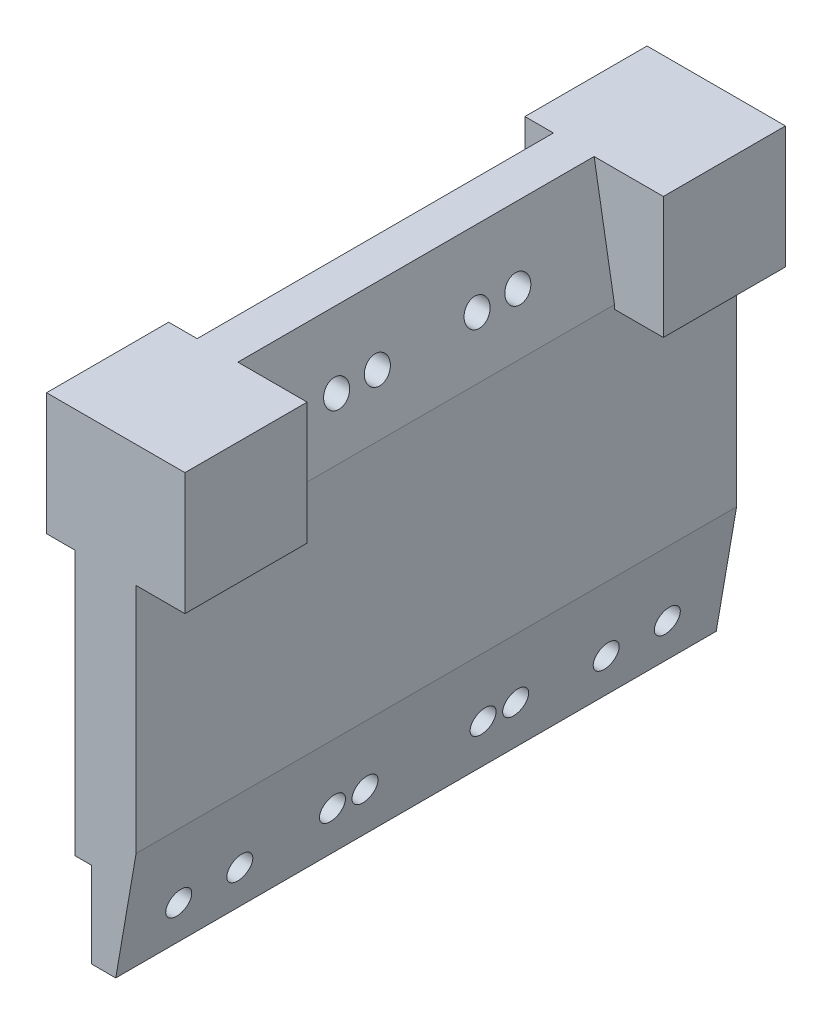
SolidWorks part; units mm, degrees
ref_plane "Front Plane" through (0, 0, 0) normal (0, 0, 1) x (1, 0, 0)
ref_plane "Top Plane" through (0, 0, 0) normal (0, 1, 0) x (1, 0, 0)
ref_plane "Right Plane" through (0, 0, 0) normal (1, 0, 0) x (0, 0, -1)
sketch "Sketch1" plane through (0, 0, 0) normal (0, 0, 1) x (1, 0, 0)
  line L1 (0, 0) -> (5, 0)
  line L2 (0, 0) -> (0, -116)
  line L3 (0, -116) -> (5, -116)
  line L4 (5, 0) -> (5, -116)
  line L5 (5, 0) -> (15, 0)
  line L6 (5, 0) -> (5, -116)
  line L7 (5, -116) -> (15, -116)
  line L8 (15, 0) -> (15, -116)
  line L9 (15, -58) -> (15, 0)
  line L10 (10, 0) -> (15, -29)
  line L11 (15, -29) -> (15, -58)
  line L13 (15, -58) -> (15, -116)
  line L14 (15, -87) -> (10, -116)
  dimension "D1" = 5
  dimension "D2" = 116
  dimension "D3" = 10
extrude "Boss-Extrude1" add sketch "Sketch1" along normal blind 73.75 and the other way blind 73.75 contours L14 L8 L9 L10 L5 L4 L7 | L4 L1 L2 L3 region at (2.5, -58, 0) region at (9.5238, -58, 0)
sketch "Sketch2" plane through (15, 0, 0) normal (1, 0, 0) x (0, 0, -1)
  line L0 (73.75, -87) -> (73.75, -116) construction
  line L1 (73.75, -116) -> (-73.75, -116) construction
  line L3 (73.75, -93.3455) -> (-73.75, -93.3455) construction
  line L4 (-73.75, -87) -> (-73.75, -116) construction
  line L5 (-73.75, -93.3455) -> (0, -93.3455) construction
  line L6 (0, -93.3455) -> (0, -116) construction
  circle A0 centre (60, -106) radius 1.5
  circle A1 centre (45, -106) radius 1.5
  circle A2 centre (22.5, -104.5) radius 1.5
  circle A3 centre (14.5, -104.5) radius 1.5
  circle A4 centre (-14.5, -104.5) radius 1.5
  circle A5 centre (-22.5, -104.5) radius 1.5
  circle A6 centre (-45, -106) radius 1.5
  circle A7 centre (-60, -106) radius 1.5
  dimension "D1" = 3
  dimension "D2" = 13.75
  dimension "D3" = 10
  dimension "D5" = 15
  dimension "D6" = 3
  dimension "D7" = 11.5
  dimension "D8" = 51.25
  dimension "D10" = 8
  dimension "D4" = 2
  dimension "D9" = 2
extrude "Cut-Extrude1" cut sketch "Sketch2" against normal through all
sketch "Sketch3" plane through (15, 0, 0) normal (1, 0, 0) x (0, 0, -1)
  line L0 (0, 0) -> (0, -111.271) construction
  line L35 (73.75, 0) -> (-73.75, 0) construction
  circle A0 centre (60, -106) radius 3.15
  circle A1 centre (45, -106) radius 3.15
  circle A2 centre (22.5, -104.5) radius 3.15
  circle A3 centre (14.5, -104.5) radius 3.15
  circle A12 centre (-14.5, -104.5) radius 3.15
  circle A13 centre (-22.5, -104.5) radius 3.15
  circle A14 centre (-45, -106) radius 3.15
  circle A15 centre (-60, -106) radius 3.15
  dimension "D1" = 6.3
  dimension "D2" = 6.3
  dimension "D3" = 6.3
  dimension "D4" = 6.3
extrude "Cut-Extrude2" cut sketch "Sketch3" against normal blind 10 contours A3 | A3 | A3 | A2 | A2 | A2 | A1 | A1 | A1 | A0 | A0 | A0 | A12 | A13 | A15 | A14 region at (15, -106, -60) region at (15, -106, -45) region at (15, -104.5, -22.5) region at (15, -104.5, -14.5) region at (15, -104.5, 14.5) region at (15, -104.5, 22.5) region at (15, -106, 60)
sketch "Sketch4" plane through (0, 0, 0) normal (-1, 0, 0) x (0, 0, 1)
  line L0 (-73.75, 0) -> (-73.75, -116) construction
  line L1 (73.75, -116) -> (-73.75, -116)
  line L2 (73.75, -116) -> (73.75, -95)
  line L3 (73.75, -95) -> (-73.75, -95)
  line L4 (-73.75, -116) -> (-73.75, -95)
  dimension "D1" = 21
extrude "Cut-Extrude3" cut sketch "Sketch4" against normal blind 4
sketch "Sketch6" plane through (15, 0, 0) normal (1, 0, 0) x (0, 0, -1)
  line L0 (0, 0) -> (0, -18.4251) construction
  line L1 (73.75, 0) -> (-73.75, 0) construction
  line L2 (73.75, 0) -> (73.75, -29) construction
  line L3 (73.75, -29) -> (-73.75, -29) construction
  circle A0 centre (12.25, -16) radius 1.65
  circle A1 centre (22.25, -16) radius 1.65
  circle A2 centre (-22.25, -16) radius 1.65
  circle A3 centre (-12.25, -16) radius 1.65
  dimension "D1" = 61.5
  dimension "D2" = 13
  dimension "D4" = 51.5
  dimension "D3" = 2
extrude "Cut-Extrude4" cut sketch "Sketch6" against normal through all
sketch "Sketch7" plane through (15, 0, 0) normal (1, 0, 0) x (0, 0, -1)
  line L0 (0, 0) -> (0, -12.96) construction
  line L1 (73.75, 0) -> (-73.75, 0) construction
  circle A0 centre (22.25, -16) radius 3.15
  circle A1 centre (12.25, -16) radius 3.15
  circle A2 centre (-12.25, -16) radius 3.15
  circle A3 centre (-22.25, -16) radius 3.15
  dimension "D1" = 6.3
  dimension "D2" = 2
extrude "Cut-Extrude6" cut sketch "Sketch7" against normal blind 10
sketch "Sketch8" plane through (0, 0, 0) normal (-1, 0, 0) x (0, 0, 1)
  line L0 (0, 0) -> (0, -53.1289) construction
  line L1 (73.75, 0) -> (43.75, 0)
  line L2 (73.75, 0) -> (73.75, -30)
  line L3 (73.75, -30) -> (43.75, -30)
  line L4 (43.75, 0) -> (43.75, -30)
  line L5 (-43.75, 0) -> (-43.75, -30)
  line L6 (-73.75, -30) -> (-43.75, -30)
  line L7 (-73.75, 0) -> (-73.75, -30)
  line L8 (-73.75, 0) -> (-43.75, 0)
  dimension "D1" = 30
  dimension "D2" = 30
extrude "Boss-Extrude2" add sketch "Sketch8" along normal blind 7
sketch "Sketch9" plane through (0, 0, 73.75) normal (0, 0, 1) x (1, 0, 0)
  line L1 (-7, -30) -> (27, -30)
  line L2 (-7, -30) -> (-7, 0)
  line L3 (-7, 0) -> (27, 0)
  line L4 (27, -30) -> (27, 0)
  dimension "D1" = 34
extrude "Boss-Extrude3" add sketch "Sketch9" against normal blind 30
sketch "Sketch10" plane through (0, 0, -73.75) normal (0, 0, -1) x (-1, 0, 0)
  line L1 (7, 0) -> (-27, 0)
  line L2 (7, 0) -> (7, -30)
  line L3 (7, -30) -> (-27, -30)
  line L4 (-27, 0) -> (-27, -30)
extrude "Boss-Extrude4" add sketch "Sketch10" against normal blind 30
